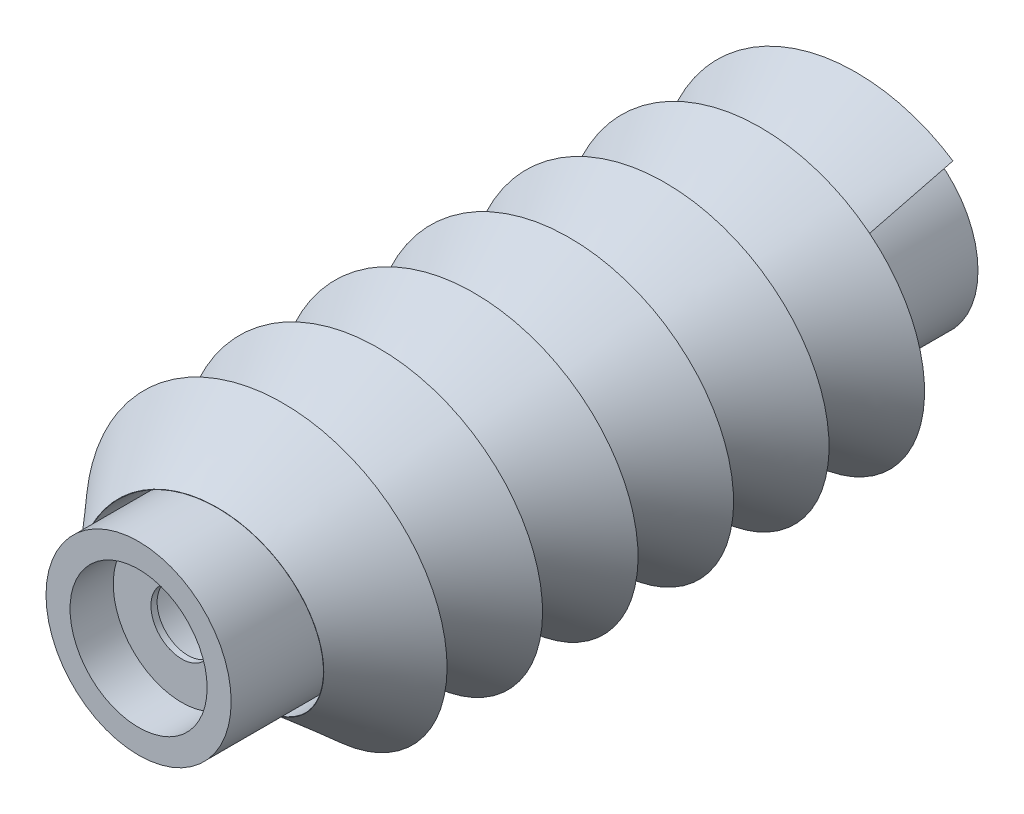
SolidWorks part; units mm, degrees
ref_plane "Спереди" through (0, 0, 0) normal (0, 0, 1) x (1, 0, 0)
ref_plane "Сверху" through (0, 0, 0) normal (0, 1, 0) x (1, 0, 0)
ref_plane "Справа" through (0, 0, 0) normal (1, 0, 0) x (0, 0, -1)
sketch "Эскиз1" plane through (0, 0, 0) normal (0, 0, 1) x (1, 0, 0)
  circle A0 centre (0, 0) radius 15
  circle A1 centre (0, 0) radius 11
  dimension "D1" = 22
  dimension "D2" = 30
extrude "Бобышка-Вытянуть1" add sketch "Эскиз1" along normal blind 63
sketch "Эскиз6" plane through (0, 0, 0) normal (0, 0, -1) x (-1, 0, 0)
  circle A0 centre (0, 0) radius 15 construction
  circle A1 centre (0, 0) radius 15
curve "Спираль1" pitch 15.4738 height 100.58 turns 6.5
ref_plane "Плоскость1" through (9.4398, 11.6572, 0) normal (-0.7669, 0.621, 0.162) x (0.119, -0.1105, 0.9867)
sketch "Эскиз7" plane through (9.4398, 11.6572, 0) normal (-0.7669, 0.621, 0.162) x (0.119, -0.1105, 0.9867)
  line L1 (0, 0) -> (16.3362, 0.9182)
  line L2 (0, 0) -> (5.6542, 10.3336)
  line L3 (5.6542, 10.3336) -> (16.3362, 0.9627)
  line L4 (16.3362, 0.9182) -> (16.3362, 0.9627)
  dimension "D1" = 16.3362
  dimension "D2" = 10
sweep "По траектории1" add profiles "Эскиз7" path "Спираль1"
sketch "Эскиз12" plane through (0, 0, 63) normal (0, 0, 1) x (1, 0, 0)
  circle A1 centre (0, 0) radius 15
  circle A2 centre (0, 0) radius 15
  dimension "D1" = 0
extrude "Бобышка-Вытянуть2" add sketch "Эскиз12" along normal blind 8
hole_wizard "Отверстие1" positions "Эскиз22" profile "Эскиз21" legacy
sketch "Эскиз22" plane through (0, 0, 71) normal (0, 0, 1) x (1, 0, 0)
  point P0 (0, 0)
sketch "Эскиз21" plane through (0, 0, 71) normal (1, 0, 0) x (0, -1, 0)
  line L0 (0, 0) -> (0, 7)
  line L1 (0, 7) -> (11.105, 7)
  line L2 (11.105, 7) -> (11.105, 0)
  line L3 (11.105, 0) -> (0, 0)
  line L4 (0, 110) -> (0, -10) construction
  dimension "Диаметр" = 22.21
  dimension "Глубина" = 7
sketch "Эскиз34" plane through (0, 0, 0) normal (0, 0, -1) x (-1, 0, 0)
  circle A1 centre (0, 0) radius 15
  circle A2 centre (0, 0) radius 15
  dimension "D1" = 0
extrude "Бобышка-Вытянуть6" add sketch "Эскиз34" along normal blind 60
move or copy body "Тело-Переместить/Копировать1" bodies to move or copy 104 copy no translate (0, 0, -50)
hole_wizard "Отверстие2" positions "Эскиз36" profile "Эскиз35" legacy
sketch "Эскиз36" plane through (0, 0, -60) normal (0, 0, -1) x (-1, 0, 0)
  point P0 (0, 0)
sketch "Эскиз35" plane through (0, 0, -60) normal (1, 0, 0) x (0, 1, 0)
  line L0 (0, 0) -> (0, 50)
  line L1 (0, 50) -> (14, 50)
  line L2 (14, 50) -> (14, 0)
  line L3 (14, 0) -> (0, 0)
  line L4 (0, 110) -> (0, -10) construction
  dimension "Диаметр" = 28
  dimension "Глубина" = 50
sketch "Эскиз43" plane through (0, 0, -10) normal (0, 0, -1) x (-1, 0, 0)
  line L2 (0.58, 2.174) -> (0.58, -2.174)
  arc A0 (0.58, 2.174) -> (0.58, -2.174) centre (0, 0) ccw
  dimension "D2" = 4.5
  dimension "D3" = 0.58
extrude "Вырез-Вытянуть2" cut sketch "Эскиз43" against normal blind 20 contours L2 A0
other "Переместить грань1" face at (-14, 0, -60) parameters "D1"=10
hole_wizard "Отверстие3" positions "Эскиз45" profile "Эскиз44" legacy
sketch "Эскиз45" plane through (0, 0, 64) normal (0, 0, 1) x (1, 0, 0)
  point P0 (0, 0)
sketch "Эскиз44" plane through (0, 0, 64) normal (1, 0, 0) x (0, -1, 0)
  line L0 (0, 0) -> (0, 20)
  line L1 (0, 20) -> (5, 20)
  line L2 (5, 20) -> (5, 0)
  line L3 (5, 0) -> (0, 0)
  line L4 (0, 110) -> (0, -10) construction
  dimension "Диаметр" = 10
  dimension "Глубина" = 20
ref_plane "Plane1" through (-0.58, -2.174, 0) normal (-0.9662, 0.2578, 0) x (0, 0, 1)
